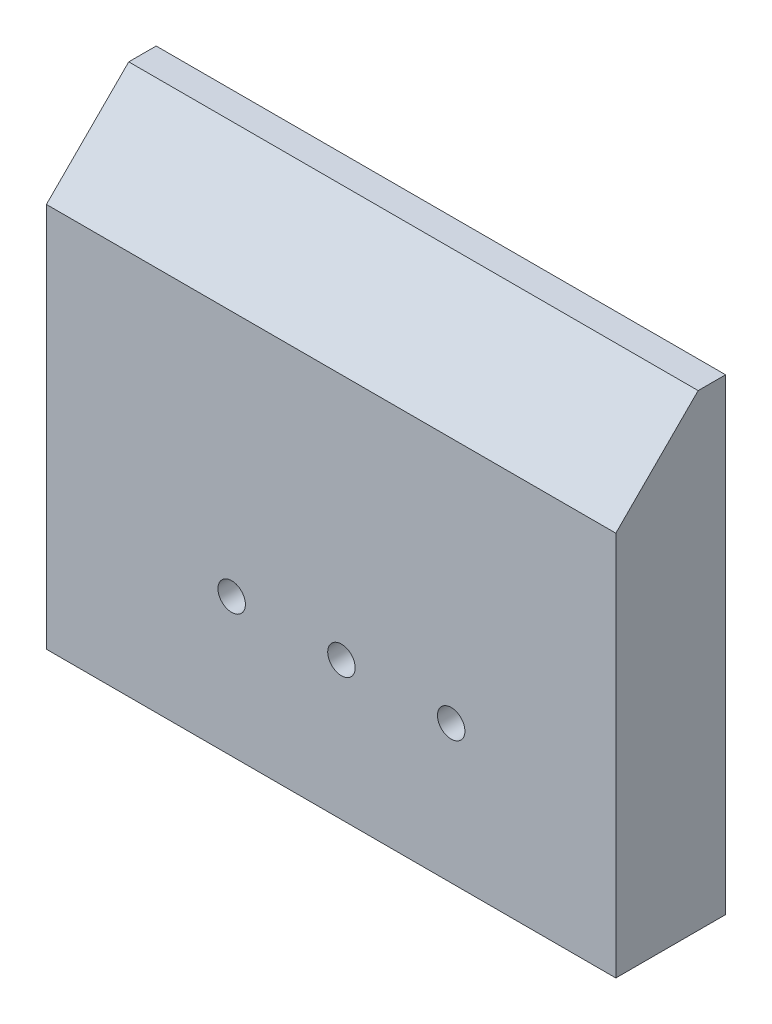
SolidWorks part; units mm, degrees
material "Delrin 2700 NC010, Low Viscosity Acetal Copolymer (SS)"
ref_plane "Front Plane" through (0, 0, 0) normal (0, 0, 1) x (1, 0, 0)
ref_plane "Top Plane" through (0, 0, 0) normal (0, 1, 0) x (1, 0, 0)
ref_plane "Right Plane" through (0, 0, 0) normal (1, 0, 0) x (0, 0, -1)
sketch "Sketch1" plane through (0, 0, 0) normal (1, 0, 0) x (0, 0, -1)
  line L0 (25.4, 0) -> (25.4, 108.2)
  line L1 (0, 0) -> (25.4, 0)
  line L2 (0, 0) -> (0, 63.5)
  line L3 (0, 63.5) -> (25.4, 63.5)
  line L4 (25.4, 0) -> (25.4, 63.5)
  line L5 (25.4, 108.2) -> (0, 108.2)
  line L6 (0, 108.2) -> (0, 0)
  line L8 (228.6, 108.2) -> (25.4, 108.2) construction
  dimension "D1" = 25.4
  dimension "D2" = 63.5
  dimension "D3" = 44.7
extrude "Boss-Extrude1" add sketch "Sketch1" along normal up to surface (131.776 mm away) contours L3 L2 L1 L0 | L5 L6 L3 L0 region at (0, 31.75, -12.7) region at (0, 85.85, -12.7)
chamfer "Chamfer1" distance 19.05 angle 45 1 edges at (65.888, 108.2, 0)
hole_wizard "1/4 (0.25) Diameter Hole1" positions "Sketch2" profile "Sketch3" hole size "1/4" standard "ANSI Inch" end condition through all
sketch "Sketch2" plane through (0, 0, 0) normal (0, 0, 1) x (1, 0, 0)
  point P8 (42.876, 32)
  point P11 (93.676, 32)
  point P14 (68.276, 32)
sketch "Sketch3" plane through (42.876, 32, 0) normal (1, 0, 0) x (0, -1, 0)
  line L0 (0, 0) -> (0, 25.4)
  line L1 (0, 25.4) -> (3.175, 25.4)
  line L2 (3.175, 25.4) -> (3.175, 0)
  line L5 (3.175, 0) -> (0, 0)
  line L11 (0, -6.35) -> (0, 107.95) construction
  dimension "Thru Hole Dia." = 6.35
  dimension "Thru Hole Depth" = 25.4
hole_wizard "Ø6.0mm Dowel Hole1" positions "Sketch4" profile "Sketch6" hole size "Ø6.0" standard "ANSI Metric"
sketch "Sketch4" plane through (0, 0, 0) normal (-1, 0, 0) x (0, 0, 1)
  point P6 (-15.4, 7)
  point P9 (-15.4, 53)
sketch "Sketch6" plane through (0, 7, -15.4) normal (0, 1, 0) x (0, 0, 1)
  line L0 (0, 0) -> (0, 10.8927)
  line L1 (0, 10.8927) -> (3.15, 9)
  line L2 (3.15, 9) -> (3.15, 0)
  line L5 (3.15, 0) -> (0, 0)
  line L10 (0, 10.8927) -> (-3.15, 9) construction
  line L11 (0, -6.35) -> (0, 107.95) construction
  dimension "Hole Dia." = 6.3
  dimension "Hole Depth" = 9
  dimension "Drill Angle" = 118
